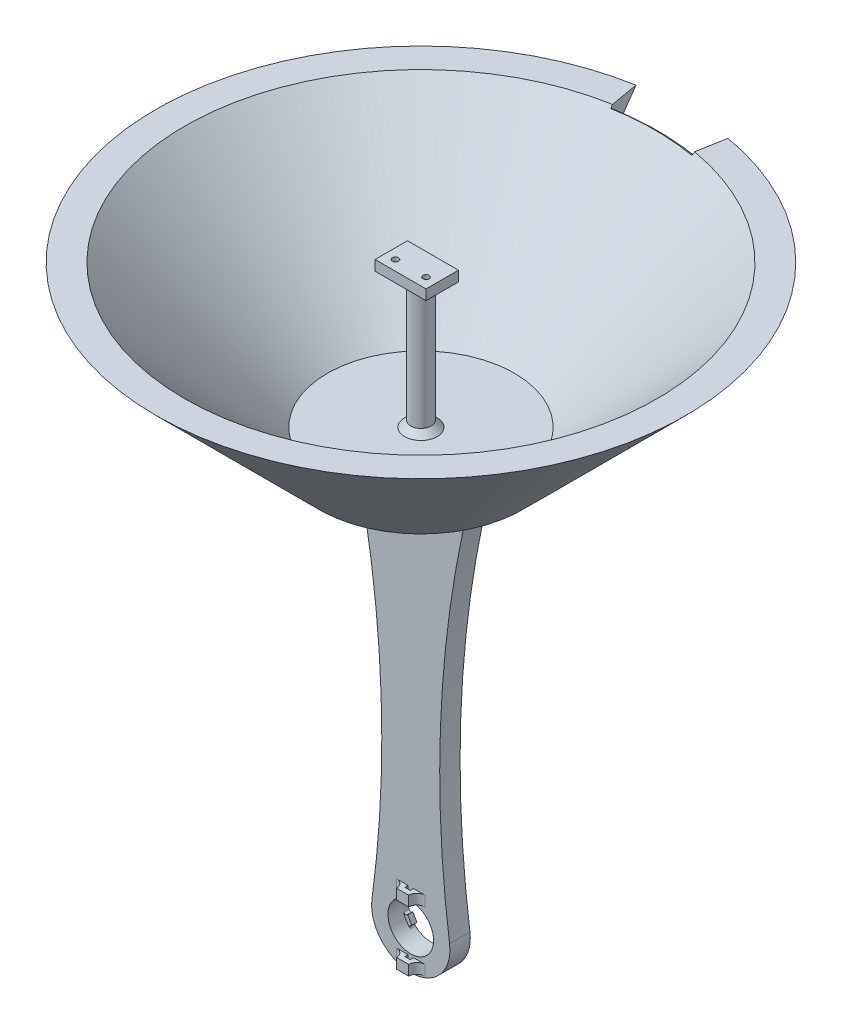
SolidWorks part; units mm, degrees
ref_plane "Front Plane" through (0, 0, 0) normal (0, 0, 1) x (1, 0, 0)
ref_plane "Top Plane" through (0, 0, 0) normal (0, 1, 0) x (1, 0, 0)
ref_plane "Right Plane" through (0, 0, 0) normal (1, 0, 0) x (0, 0, -1)
sketch "Sketch1" plane through (0, 0, 0) normal (0, 0, 1) x (1, 0, 0)
  line L0 (0, 0) -> (0, 200) construction
  line L1 (-15, 101.836) -> (15, 101.836) construction
  line L2 (-30, 200) -> (30, 200)
  circle A0 centre (0, 0) radius 11.2
  circle A1 centre (0, 0) radius 19.2
  arc A2 (-19.0212, 2.6141) -> (-30, 200) centre (-531.8309, 73.0894) ccw
  arc A3 (19.0212, 2.6141) -> (30, 200) centre (531.8309, 73.0894) cw
  point P10 (-15, 101.836)
  point P12 (15, 101.836)
  dimension "D1" = 22.4
  dimension "D2" = 8
  dimension "60" = 60
  dimension "D4" = 30
  dimension "D5" = 200
extrude "Boss-Extrude1" add sketch "Sketch1" along normal blind 10 contours A1 A3 L2 A2 | A1 A0 region at (0, 118.4726, 0) region at (0, 18.6569, 0)
sketch "Sketch2" plane through (0, 0, 0) normal (0, 0, -1) x (-1, 0, 0)
  line L0 (0, 11.2) -> (0, 0) construction
  line L6 (-2, 13.2) -> (2, 13.2)
  line L7 (-2, 13.2) -> (-2, 9.2)
  line L8 (-2, 9.2) -> (2, 9.2)
  line L9 (2, 13.2) -> (2, 9.2)
  line L10 (-2, 13.2) -> (2, 9.2) construction
  line L11 (-2, 9.2) -> (2, 13.2) construction
  circle A0 centre (0, 0) radius 11.2 construction
  point P0 (0, 11.2)
  dimension "D1" = 4
  dimension "D2" = 4
ref_axis "Axis1" through (0, 0, 10) along (0, 0, -1)
sketch "Sketch3" plane through (0, 0, 10) normal (0, 0, 1) x (1, 0, 0)
  line L0 (0, 0) -> (0, 22.4)
  line L1 (-5.9851, 0) -> (43.2633, 0) construction
  line L2 (-3, 17.2) -> (3, 17.2)
  line L3 (-3, 17.2) -> (-3, 12.2)
  line L4 (-3, 12.2) -> (3, 12.2)
  line L5 (3, 17.2) -> (3, 12.2)
  line L6 (-3, 17.2) -> (3, 12.2) construction
  line L7 (-3, 12.2) -> (3, 17.2) construction
  line L8 (-3, -12.2) -> (3, -12.2)
  line L9 (3, -17.2) -> (3, -12.2)
  line L10 (-3, -17.2) -> (3, -17.2)
  line L11 (-3, -17.2) -> (-3, -12.2)
  line L12 (0, 11.2) -> (7.4681, 11.2) construction
  circle A1 centre (0, 0) radius 11.2 construction
  point P2 (0, 14.7)
  dimension "D1" = 5
  dimension "D2" = 6
  dimension "D3" = 1
extrude "Boss-Extrude3" add sketch "Sketch3" along normal blind 4 contours L5 L2 L0 L4 | L3 L4 L0 L2 | L11 L10 L9 L8 region at (-1.5, 14.7, 10) region at (1.5, 14.7, 10) region at (0, -14.7, 10)
fillet "Fillet6" radius 4 4 edges at (-3, -14.7, 10) (3, -14.7, 10) (3, 14.7, 10) (-3, 14.7, 10)
sketch "Sketch5" plane through (0, 17.2, 0) normal (0, 1, 0) x (1, 0, 0)
  line L0 (-30, -10) -> (30, -10) construction
  line L1 (-1.3, -10) -> (1.3, -10)
  line L2 (-1.3, -10) -> (-1.3, -11.6)
  line L3 (-1.3, -11.6) -> (1.3, -11.6)
  line L4 (1.3, -10) -> (1.3, -11.6)
  point P6 (0, -10)
  dimension "D1" = 1.6
  dimension "D2" = 2.6
extrude "Cut-Extrude1" cut sketch "Sketch5" against normal through all both
sketch "Sketch6" plane through (0, 0, 0) normal (1, 0, 0) x (0, 0, -1)
  line L0 (-5, 200) -> (45, 200)
  line L1 (45, 200) -> (125, 280)
  line L2 (125, 280) -> (-5, 280)
  line L3 (-5, 200) -> (-5, 280)
  line L4 (-10, 200) -> (0, 200) construction
  line L5 (40.8579, 210) -> (100.8579, 270)
  line L6 (100.8579, 270) -> (5, 270)
  line L7 (5, 210) -> (5, 270)
  line L8 (5, 210) -> (40.8579, 210)
  line L9 (5, 210) -> (-5, 210)
  line L10 (100.8579, 270) -> (110.8579, 280)
  point P4 (-5, 200)
  dimension "D1" = 50
  dimension "D2" = 130
  dimension "D3" = 45
  dimension "D4" = 10
revolve "Revolve1" add sketch "Sketch6" angle 360 about L3 region at (0, 205, 3.4736)
fillet "Fillet7" radius 20 2 edges at (0, 200, 0) (0, 200, 10)
sketch "Sketch7" plane through (0, 210, 0) normal (0, 1, 0) x (1, 0, 0)
  circle A0 centre (0, -5) radius 45.8579 construction
  circle A1 centre (0, -5) radius 45.8579
  circle A2 centre (0, -5) radius 5
  dimension "D1" = 10
extrude "Boss-Extrude4" add sketch "Sketch7" along normal blind 65 separate body contours A2 region at (0, 210, 5)
sketch "Sketch8" plane through (0, 275, 0) normal (0, 1, 0) x (1, 0, 0)
  line L1 (-12.5, -15) -> (12.5, -15)
  line L2 (-12.5, -15) -> (-12.5, 5)
  line L3 (-12.5, 5) -> (12.5, 5)
  line L4 (12.5, -15) -> (12.5, 5)
  line L5 (-12.5, -15) -> (12.5, 5) construction
  line L6 (-12.5, 5) -> (12.5, -15) construction
  circle A1 centre (0, -5) radius 5
  circle A2 centre (0, -5) radius 5
  circle M4 centre (0, -5) radius 5
  dimension "D2" = 20
  dimension "D3" = 25
  dimension "D1" = 0
extrude "Boss-Extrude5" add sketch "Sketch8" along normal blind 5 contours L1 L4 L3 M4 | M4 | L3 L2 L1 M4 region at (-12.1798, 275, 5) region at (0, 275, 5)
sketch "Sketch10" plane through (0, 280, 0) normal (0, 1, 0) x (1, 0, 0)
  line L0 (0, -15) -> (0, 14.608) construction
  line L1 (-12.5, -15) -> (12.5, -15) construction
  line L2 (0, -10) -> (0, 0) construction
  line L3 (-7.5, -10) -> (-7.5, -8.5) construction
  line L4 (-7.5, -10) -> (-9, -10) construction
  line L6 (-12.5, -15) -> (-12.5, 5) construction
  circle A0 centre (-7.5, -10) radius 1.5
  circle A1 centre (7.5, -10) radius 1.5
  point P17 (-12.5, -5)
  dimension "D1" = 3
  dimension "D2" = 7.5
  dimension "D3" = 5
  dimension "D4" = 15
  dimension "D5" = 5
  dimension "D6" = 7.5
extrude "Cut-Extrude2" cut sketch "Sketch10" against normal up to next (5 mm away)
fillet "Fillet8" radius 1 1 edges at (0, 275, 10)
ref_plane "Plane1" through (0, 0, 5) normal (0, 0, 1) x (1, 0, 0)
sketch "Sketch12" plane through (0, 0, 5) normal (0, 0, 1) x (1, 0, 0)
  line L0 (5, 213) -> (8, 210)
  line L1 (5, 210) -> (5, 274) construction
  line L2 (45.8579, 210) -> (-45.8579, 210) construction
  line L3 (8, 210) -> (5, 210)
  line L4 (5, 210) -> (5, 213)
  line L5 (0, 210) -> (0, 266.2577)
  dimension "D1" = 3
  dimension "D2" = 3
revolve "Revolve2" add sketch "Sketch12" angle 360 about L5 region at (6, 211, 5)
extrude "Boss-Extrude6" add sketch "Sketch2" against normal blind 2.5
pattern_circular "CirPattern1" count 3 over 360 about axis through (0, 0, 10) along (0, 0, -1) of "Boss-Extrude6"
fillet "Fillet9" radius 1 6 edges at (2, 11.02, 1.25) (-2, 11.02, 1.25) (8.5436, -7.242, 1.25) (10.5436, -3.7779, 1.25) (-8.5436, -7.242, 1.25) (-10.5436, -3.7779, 1.25)
ref_axis "Axis3" through (0, 274, 5) along (0, -1, 0)
sketch "Sketch13" plane through (0, 0, 0) normal (1, 0, 0) x (0, 0, -1)
  line L0 (45, 200) -> (125, 280) construction
  line L1 (125, 280) -> (-135, 280) construction
  line L2 (45, 200) -> (111.3431, 266.3431)
  line L3 (105.6863, 280) -> (-135, 280)
  line L4 (105.6863, 280) -> (125, 280)
  line L5 (125, 280) -> (111.3431, 266.3431)
  arc A0 (111.3431, 266.3431) -> (105.6863, 280) centre (105.6863, 272) ccw
  dimension "D1" = 8
revolve "Cut-Revolve1" cut sketch "Sketch13" angle 20 mid plane about axis through (0, 274, 5) along (0, -1, 0) region at (0, 276.4455, -116.4186)
sketch "Sketch14" plane through (0, 280, 0) normal (0, 1, 0) x (1, 0, 0)
  line L0 (-9.4113, -12.5) -> (10.1269, -12.5)
  line L1 (7.5, -10) -> (7.5, -11.5)
  line L2 (-12.5, 0.9) -> (12.5, 0.9)
  line L3 (12.5, -15) -> (12.5, 5) construction
  line L4 (-12.5, -15) -> (-12.5, 5) construction
  line L6 (-12.5, 5) -> (12.5, 5)
  line L7 (-12.5, 5) -> (-12.5, 0.9)
  line L8 (-12.5, 0.9) -> (12.5, 0.9)
  line L9 (12.5, 5) -> (12.5, 0.9)
  circle A0 centre (7.5, -10) radius 1.5 construction
  point P2 (7.5, -11.5)
  line M10 (12.5, -15) -> (12.5, 5)
  line M11 (12.5, 5) -> (-12.5, 5)
  line M12 (-12.5, 5) -> (-12.5, -15)
  dimension "D1" = 1
  dimension "D2" = 13.4
extrude "Cut-Extrude3" cut sketch "Sketch14" against normal up to next contours L2 M12 M10 M11 region at (0, 280, -2.95)
